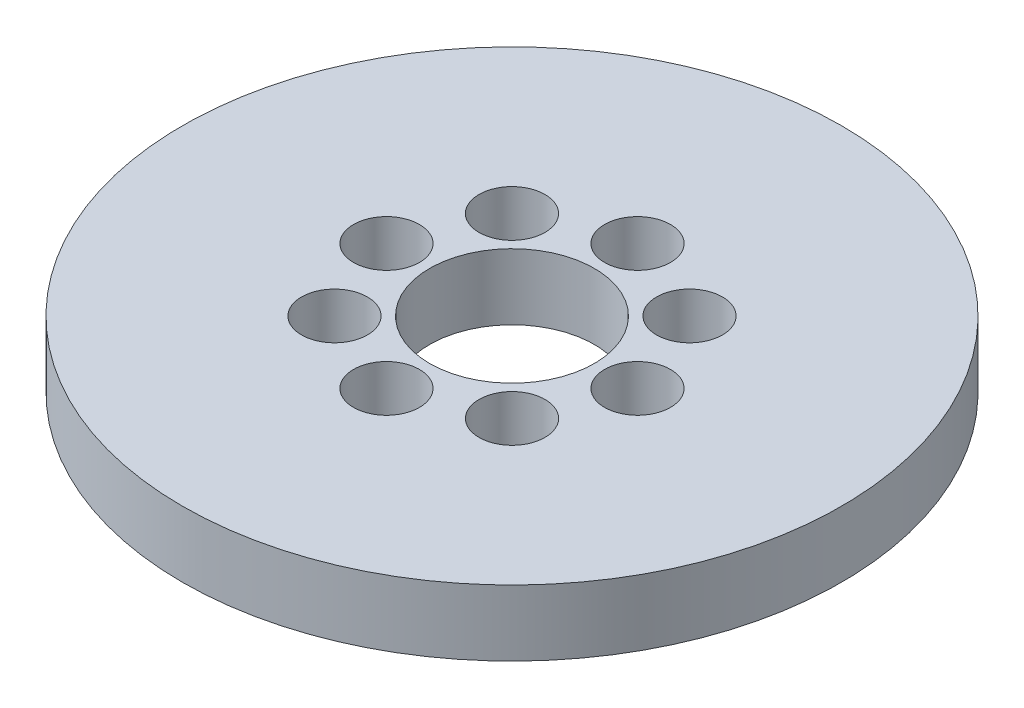
SolidWorks part; units mm, degrees
ref_plane "Front Plane" through (0, 0, 0) normal (0, 0, 1) x (1, 0, 0)
ref_plane "Top Plane" through (0, 0, 0) normal (0, 1, 0) x (1, 0, 0)
ref_plane "Right Plane" through (0, 0, 0) normal (1, 0, 0) x (0, 0, -1)
sketch "Sketch1" plane through (0, 0, 0) normal (0, 1, 0) x (1, 0, 0)
  circle A0 centre (0, 0) radius 100
  dimension "FLANGE_OD" = 200
extrude "Boss-Extrude1" add sketch "Sketch1" along normal blind 20
sketch "Sketch2" plane through (0, 0, 0) normal (0, 1, 0) x (1, 0, 0)
  circle A0 centre (0, 0) radius 25
  dimension "BORE_D" = 50
extrude "Cut-Extrude1" cut sketch "Sketch2" along normal through all
sketch "Sketch3" plane through (0, 20, 0) normal (0, 1, 0) x (1, 0, 0)
  circle A0 centre (0, 0) radius 38.089 construction
  circle A1 centre (-38.089, 0) radius 10
  dimension "BOLT_D" = 20
  dimension "BOLT_PCD" = 76.1781
extrude "Cut-Extrude2" cut sketch "Sketch3" against normal blind 17.8388
pattern_circular "CirPattern1" count 8 over 360 about axis through (0, 0, 0) along (0, 1, 0) of "Cut-Extrude2"
